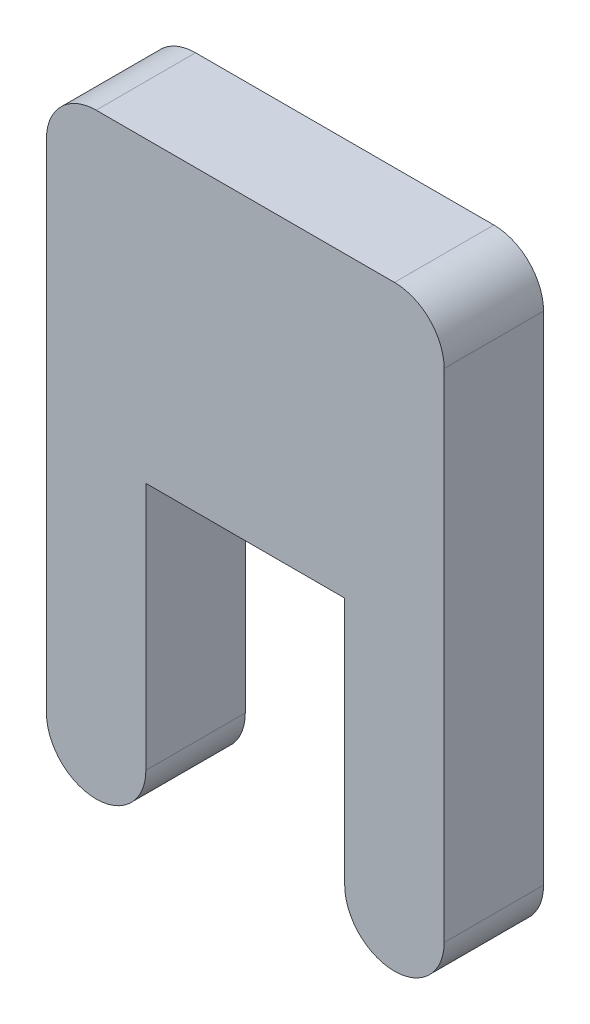
SolidWorks part; units mm, degrees
material "Maple"
ref_plane "Front Plane" through (0, 0, 0) normal (0, 0, 1) x (1, 0, 0)
ref_plane "Top Plane" through (0, 0, 0) normal (0, 1, 0) x (1, 0, 0)
ref_plane "Right Plane" through (0, 0, 0) normal (1, 0, 0) x (0, 0, -1)
sketch "Sketch1" plane through (0, 0, 0) normal (0, 0, 1) x (1, 0, 0)
  line L1 (-5, -7.5) -> (5, -7.5)
  line L2 (-5, -7.5) -> (-5, 7.5)
  line L3 (-5, 7.5) -> (5, 7.5)
  line L4 (5, -7.5) -> (5, 7.5)
  line L5 (-5, -7.5) -> (5, 7.5) construction
  line L6 (-5, 7.5) -> (5, -7.5) construction
  line L7 (-2.5, 0) -> (2.5, 0)
  line L8 (-2.5, 0) -> (-2.5, -7.5)
  line L9 (-2.5, -7.5) -> (2.5, -7.5)
  line L10 (2.5, 0) -> (2.5, -7.5)
  line L11 (-2.5, 0) -> (2.5, -7.5) construction
  line L12 (-2.5, -7.5) -> (2.5, 0) construction
  point P0 (0, 0)
  point P6 (0, -3.75)
  point P11 (0, 0)
  dimension "D1" = 15
  dimension "D2" = 10
  dimension "D3" = 2.5
extrude "Boss-Extrude1" add sketch "Sketch1" along normal mid plane 2.5 contours L7 L10 L1 L4 L3 L2 L8 region at (0, 1.25, 0)
fillet "Fillet1" radius 1.25 6 edges at (-2.5, -7.5, 0) (-5, -7.5, 0) (-5, 7.5, 0) (5, 7.5, 0) (2.5, -7.5, 0) (5, -7.5, 0)
